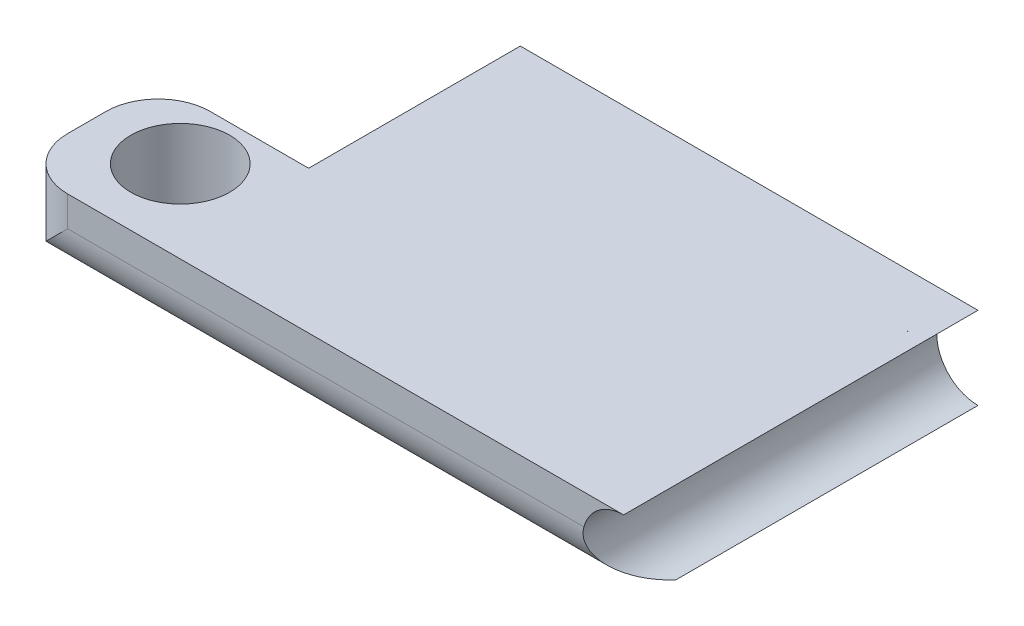
SolidWorks part; units mm, degrees
ref_plane "Front Plane" through (0, 0, 0) normal (0, 0, 1) x (1, 0, 0)
ref_plane "Top Plane" through (0, 0, 0) normal (0, 1, 0) x (1, 0, 0)
ref_plane "Right Plane" through (0, 0, 0) normal (1, 0, 0) x (0, 0, -1)
sketch "Sketch1" plane through (0, 0, 0) normal (0, 0, 1) x (1, 0, 0)
  line L0 (0, 150) -> (0, 0)
  line L1 (0, 150) -> (1106.9725, 150)
  line L3 (0, 0) -> (1106.9725, 0)
  line L4 (1106.9725, 150) -> (1106.9725, 0)
extrude "Boss-Extrude1" add sketch "Sketch1" along normal blind 645 contours L1 L4 L3 L0
sketch "Sketch2" plane through (0, 0, 0) normal (0, -1, 0) x (1, 0, 0)
  line L0 (0, 645) -> (0, 0) construction
  line L1 (0, 645) -> (1106.9725, 645) construction
  circle A0 centre (150, 495) radius 90
  dimension "D1" = 180
  dimension "D2" = 150
  dimension "D3" = 150
extrude "Cut-Extrude1" cut sketch "Sketch2" against normal through all contours A0
sketch "Sketch3" plane through (0, 0, 0) normal (0, -1, 0) x (1, 0, 0)
  line L1 (0, 0) -> (273.9363, 0)
  line L2 (0, 0) -> (0, 385.2587)
  line L3 (0, 385.2587) -> (273.9363, 385.2587)
  line L4 (273.9363, 0) -> (273.9363, 385.2587)
extrude "Cut-Extrude2" cut sketch "Sketch3" against normal through all
sketch "Sketch5" plane through (0, 0, 645) normal (0, 0, 1) x (1, 0, 0)
  line L0 (1106.9725, 150) -> (1106.9725, 0) construction
  line L2 (1106.9725, 150) -> (1106.9725, 0)
  arc A0 (1106.9725, 0) -> (1106.9725, 150) centre (1106.9725, 75) cw
extrude "Cut-Extrude3" cut sketch "Sketch5" against normal through all
fillet "Fillet1" radius 95 3 edges at (553.4863, 0, 645) (0, 75, 645) (0, 75, 385.2587)
fillet "Fillet2" radius 95 1 edges at (273.9363, 0, 192.6294)
